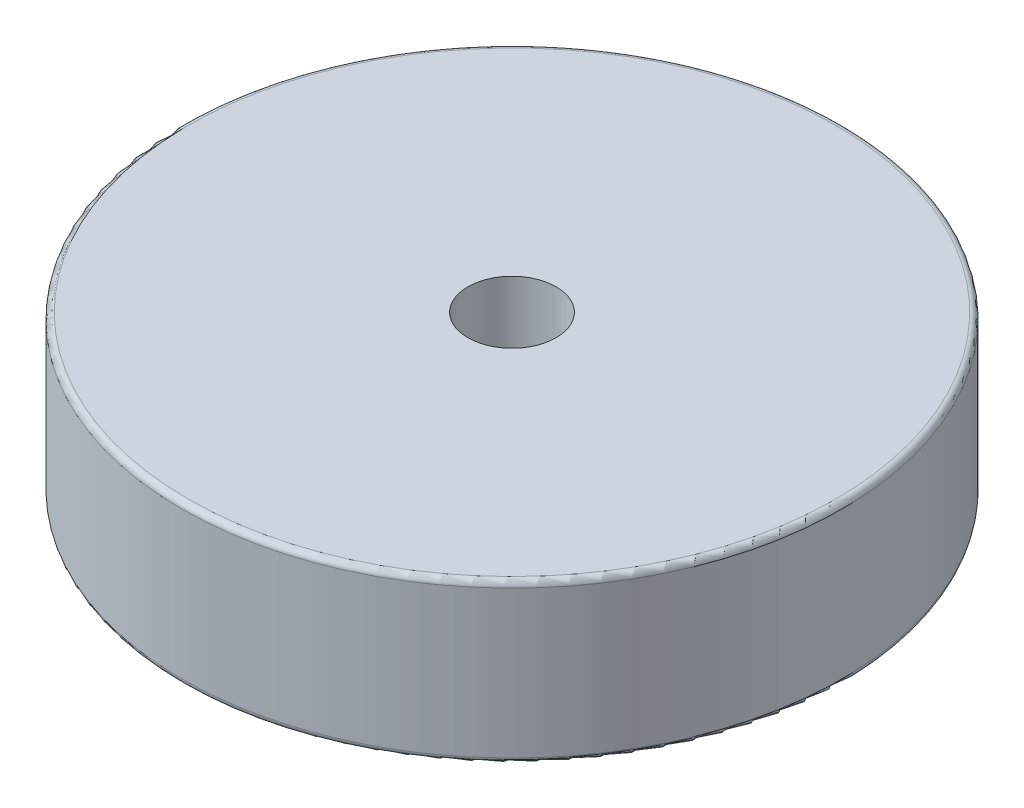
SolidWorks part; units mm, degrees
material "Литая нержавеющая сталь"
ref_plane "Спереди" through (0, 0, 0) normal (0, 0, 1) x (1, 0, 0)
ref_plane "Сверху" through (0, 0, 0) normal (0, 1, 0) x (1, 0, 0)
ref_plane "Справа" through (0, 0, 0) normal (1, 0, 0) x (0, 0, -1)
sketch "Эскиз1" plane through (0, 0, 0) normal (0, 1, 0) x (1, 0, 0)
  circle A0 centre (0, 0) radius 56
  dimension "D1" = 112
extrude "Бобышка-Вытянуть1" add sketch "Эскиз1" against normal blind 27
sketch "Эскиз3" plane through (0, -27, 0) normal (0, -1, 0) x (-1, 0, 0)
  circle A0 centre (0, 0) radius 29.5
  dimension "D1" = 59
extrude "Бобышка-Вытянуть2" add sketch "Эскиз3" along normal blind 5
fillet "Скругление1" radius 5 1 edges at (0, -32, -29.5)
sketch "Эскиз6" plane through (0, -32, 0) normal (0, -1, 0) x (1, 0, 0)
  circle A0 centre (0, 0) radius 7.5
  dimension "D1" = 15
extrude "Вырез-Вытянуть1" cut sketch "Эскиз6" against normal blind 33 contours A0
fillet "Скругление2" radius 1 1 edges at (0, -32, -7.5)
fillet "Скругление3" radius 1 2 edges at (0, -27, 56) (0, 0, 56)
